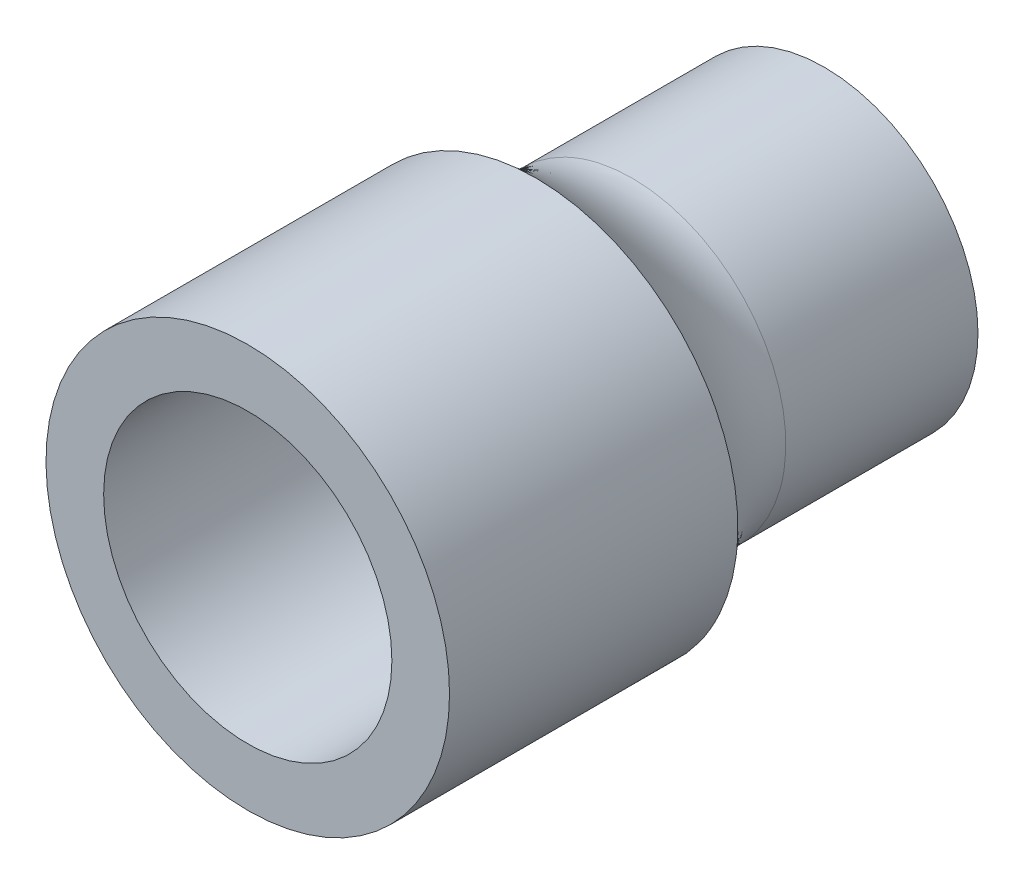
SolidWorks part; units mm, degrees
ref_plane "前视基准面" through (0, 0, 0) normal (0, 0, 1) x (1, 0, 0)
ref_plane "上视基准面" through (0, 0, 0) normal (0, 1, 0) x (1, 0, 0)
ref_plane "右视基准面" through (0, 0, 0) normal (1, 0, 0) x (0, 0, -1)
sketch "草图1" plane through (0, 0, 0) normal (0, 0, 1) x (1, 0, 0)
  circle A0 centre (0, 0) radius 6
  circle A1 centre (0, 0) radius 8
  dimension "D1" = 12
  dimension "D2" = 16
extrude "凸台-拉伸1" add sketch "草图1" along normal blind 10
sketch "草图2" plane through (0, 0, 10) normal (0, 0, 1) x (1, 0, 0)
  circle A0 centre (0, 0) radius 8
ref_plane "基准面1" through (0, 0, 15) normal (0, 0, 1) x (1, 0, 0)
sketch "草图3" plane through (0, 0, 15) normal (0, 0, 1) x (1, 0, 0)
  circle A0 centre (0, 0) radius 10.5
  dimension "D1" = 21
loft "放样1" add profiles "草图3", "草图2" connector at (-10.0922, 2.8977, 15) connector at (-4.2484, 6.7788, 10)
sketch "草图4" plane through (0, 0, 15) normal (0, 0, 1) x (1, 0, 0)
  circle A0 centre (0, 0) radius 10.5
  circle A1 centre (0, 0) radius 7.5
  dimension "D1" = 15
extrude "凸台-拉伸2" add sketch "草图4" along normal blind 15
sketch "草图5" plane through (0, 0, 10) normal (0, 0, -1) x (-1, 0, 0)
  circle A0 centre (0, 0) radius 6
sketch "草图6" plane through (0, 0, 15) normal (0, 0, 1) x (1, 0, 0)
  circle A0 centre (0, 0) radius 7.5
loft "切除-放样1" cut profiles "草图6", "草图5" connector at (-6.538, 3.6749, 15) connector at (-5.0538, 3.234, 10)
